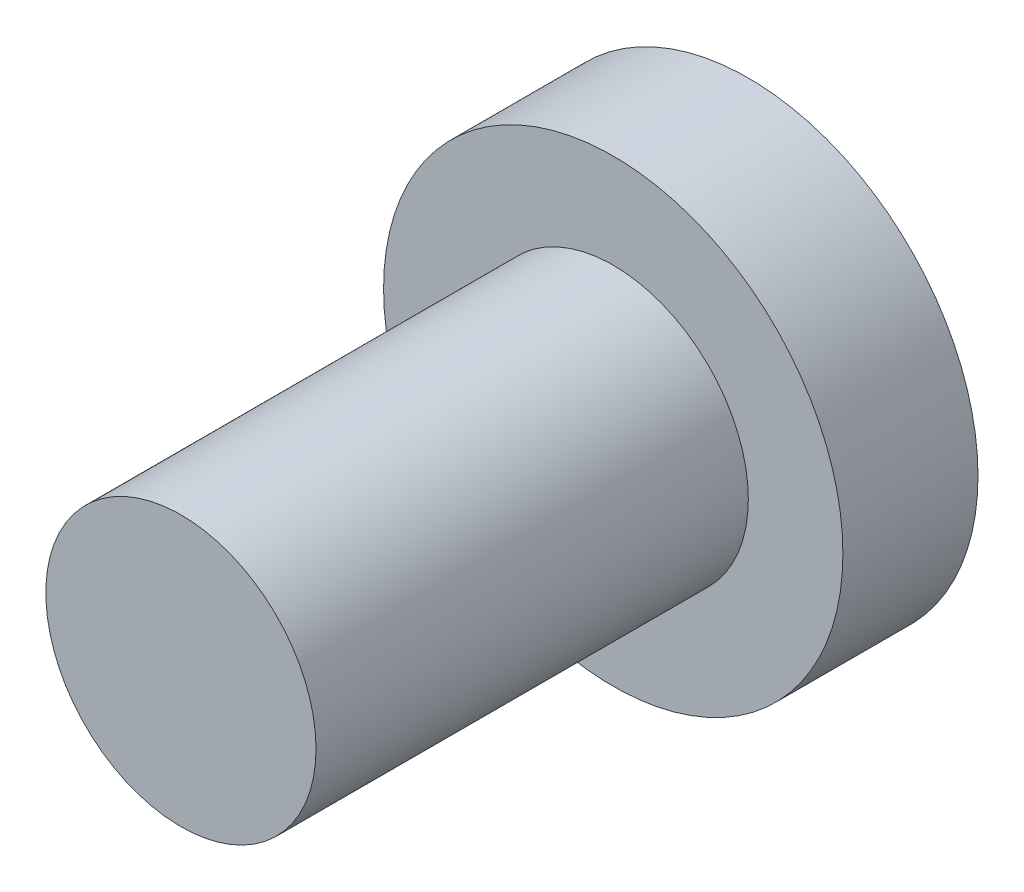
SolidWorks part; units mm, degrees
material "Chrome Stainless Steel"
ref_plane "Front Plane" through (0, 0, 0) normal (0, 0, 1) x (1, 0, 0)
ref_plane "Top Plane" through (0, 0, 0) normal (0, 1, 0) x (1, 0, 0)
ref_plane "Right Plane" through (0, 0, 0) normal (1, 0, 0) x (0, 0, -1)
sketch "Sketch1" plane through (0, 0, 0) normal (0, 0, 1) x (1, 0, 0)
  circle A0 centre (0, 0) radius 4.25
  circle A1 centre (0, 0) radius 2.5
  dimension "D1" = 8.5
  dimension "D2" = 5
extrude "Boss-Extrude3" add sketch "Sketch1" against normal blind 2.5 contours A0 A1 | A1 region at (-4.1298, 0, 0) region at (0, 0, 0)
extrude "Boss-Extrude4" add sketch "Sketch1<3>" along normal blind 8 contours A1 region at (0, 0, 0)
sketch "Sketch1<3>" plane through (0, 0, 0) normal (0, 0, 1) x (1, 0, 0) same geometry as "Sketch1"
